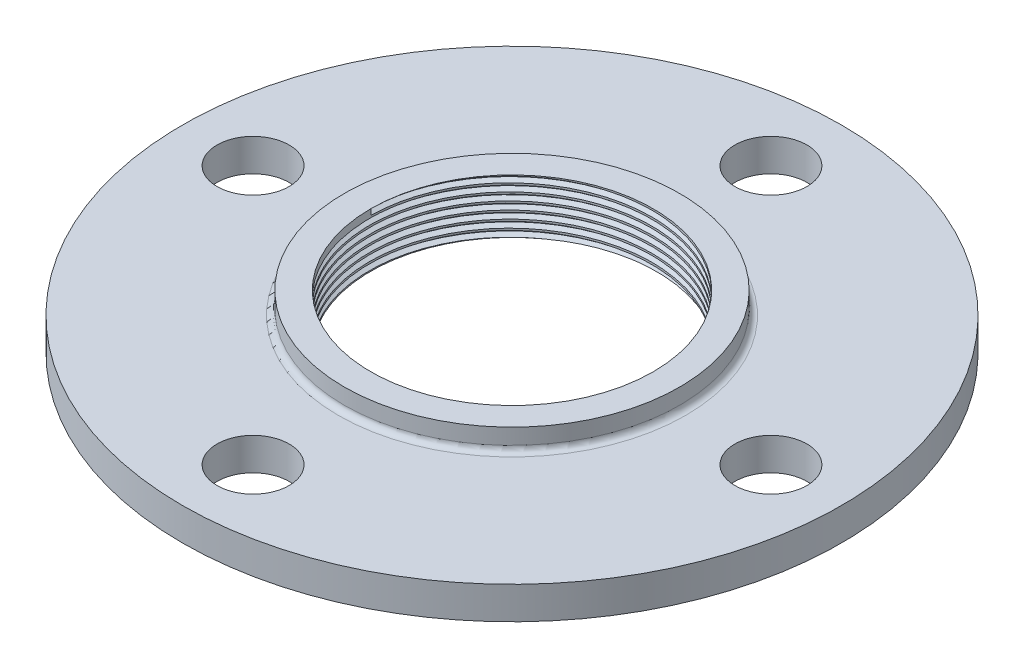
SolidWorks part; units mm, degrees
material "Plain Carbon Steel"
ref_plane "Front Plane" through (0, 0, 0) normal (0, 0, 1) x (1, 0, 0)
ref_plane "Top Plane" through (0, 0, 0) normal (0, 1, 0) x (1, 0, 0)
ref_plane "Right Plane" through (0, 0, 0) normal (1, 0, 0) x (0, 0, -1)
sketch "Sketch1" plane through (0, 0, 0) normal (0, 1, 0) x (1, 0, 0)
  circle A0 centre (0, 0) radius 88.9
  circle A1 centre (0, 0) radius 69.85 construction
  circle A2 centre (0, 69.85) radius 9.7234
  circle A3 centre (69.85, 0) radius 9.7234
  circle A4 centre (0, -69.85) radius 9.7234
  circle A5 centre (-69.85, 0) radius 9.7234
  point P15 (0, 0)
  dimension "D1" = 139.7
  dimension "D2" = 177.8
  dimension "D3" = 19.4469
  dimension "D4" = 4
extrude "Boss-Extrude1" add sketch "Sketch1" along normal blind 8.763
sketch "Sketch2" plane through (0, 8.763, 0) normal (0, 1, 0) x (1, 0, 0)
  circle A0 centre (0, 0) radius 45.2437
  circle A1 centre (0, 0) radius 38.1
  dimension "D1" = 76.2
  dimension "D2" = 90.4875
extrude "Boss-Extrude2" add sketch "Sketch2" along normal blind 5.842
fillet "Fillet1" radius 1.5875 1 edges at (0, 8.763, 45.2437)
sketch "Sketch3" plane through (0, 8.763, 0) normal (0, 1, 0) x (1, 0, 0)
  circle A0 centre (0, 0) radius 38.1
extrude "Cut-Extrude1" cut sketch "Sketch3" against normal through all
thread "Thread1" pitch 2.1167 method cut profile "Thread Profile1" start angle 0, offset 0, length 0, pitch 2.1167, diameter 76.2
ref_plane "Plane1" through (-38.1, 14.605, 0) normal (0, 0, 1) x (-1, 0, 0)
sketch "Thread Profile1" plane through (-38.1, 14.605, 0) normal (0, 0, 1) x (-1, 0, 0)
  line L0 (0, 0) -> (0, 2.1167) construction
  line L1 (0, 0) -> (1.1457, 0.6615)
  line L2 (1.1457, 0.6615) -> (1.1457, 0.926)
  line L3 (1.1457, 0.926) -> (0, 1.5875)
  line L4 (1.1457, 0.7937) -> (0, 0.7937) construction
  line L11 (0, 0) -> (0, 1.5875)
  point P2 (0, 0)
  dimension "Pitch" = 2.1167
  dimension "Profile_Angle" = 60
  dimension "Profile_Land" = 0.2646
  dimension "Profile_Height" = 1.1457
